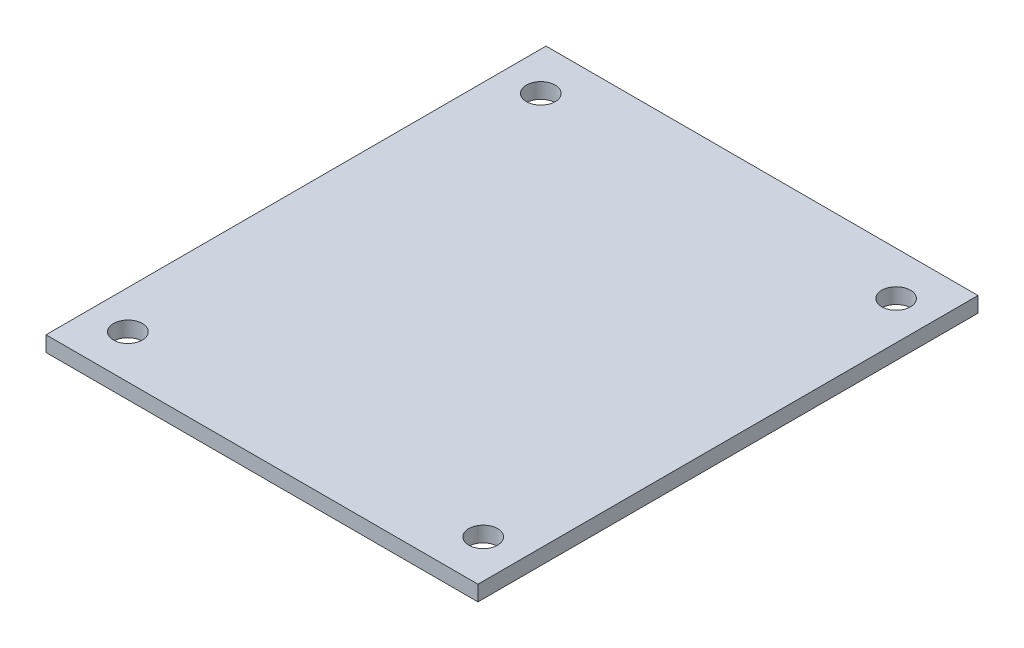
SolidWorks part; units mm, degrees
ref_plane "Front Plane" through (0, 0, 0) normal (0, 0, 1) x (1, 0, 0)
ref_plane "Top Plane" through (0, 0, 0) normal (0, 1, 0) x (1, 0, 0)
ref_plane "Right Plane" through (0, 0, 0) normal (1, 0, 0) x (0, 0, -1)
sketch "Sketch1" plane through (0, 0, 0) normal (0, 1, 0) x (1, 0, 0)
  line L1 (0, 0) -> (44.9834, 0)
  line L2 (0, 0) -> (0, 52.07)
  line L3 (0, 52.07) -> (44.9834, 52.07)
  line L4 (44.9834, 0) -> (44.9834, 52.07)
  circle A0 centre (3.9917, 47.535) radius 1.5
  circle A1 centre (40.9917, 47.535) radius 1.5
  circle A2 centre (40.9917, 4.535) radius 1.5
  circle A3 centre (3.9917, 4.535) radius 1.5
  point P13 (0, 0)
  point P14 (0, 0)
  point P15 (0, 0)
  point P16 (0, 0)
  point P17 (0, 0)
  dimension "D5" = 3
  dimension "D1" = 44.9834
  dimension "D2" = 52.07
  dimension "D3" = 43
  dimension "D4" = 37
  dimension "D6" = 3.9917
  dimension "D7" = 4.535
extrude "Boss-Extrude1" add sketch "Sketch1" along normal blind 1.6
equation "\"D6@Sketch1\"=(\"D1@Sketch1\"-\"D4@Sketch1\")/2"
equation "\"D7@Sketch1\"=(\"D2@Sketch1\"-\"D3@Sketch1\")/2"
